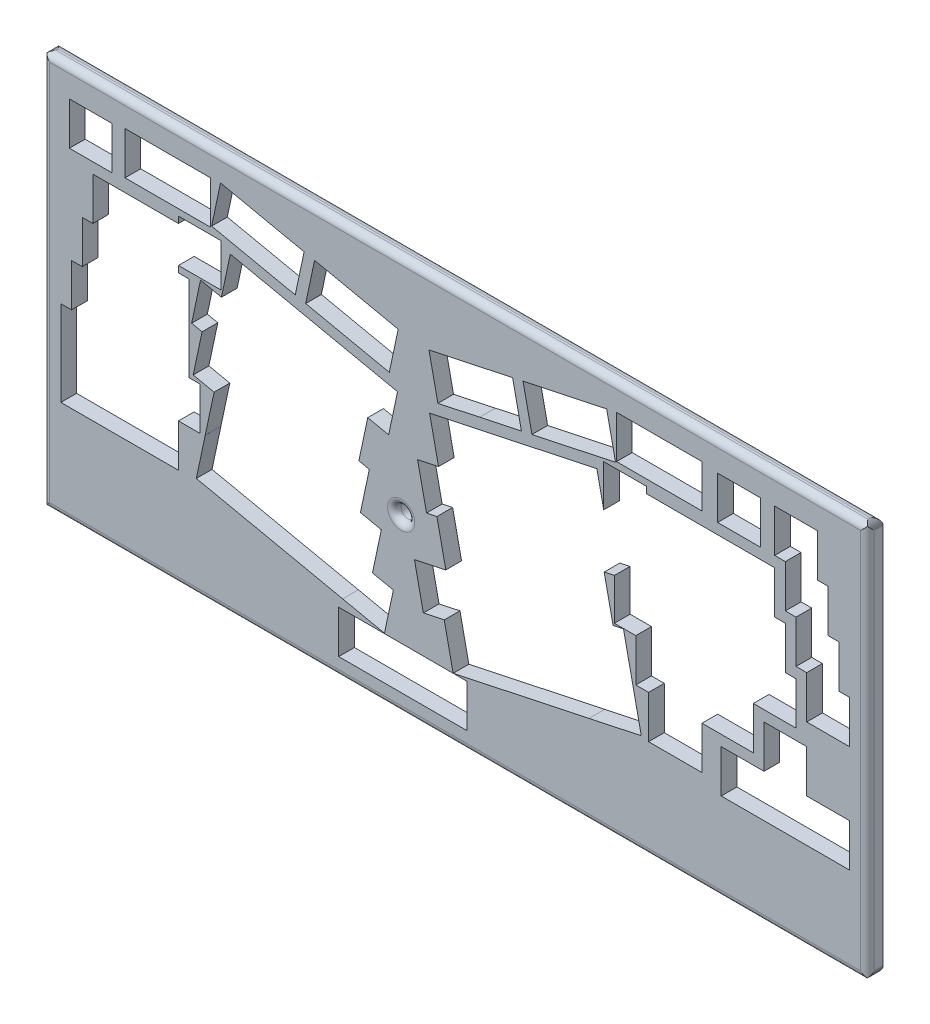
SolidWorks part; units mm, degrees
ref_plane "Front Plane" through (0, 0, 0) normal (0, 0, 1) x (1, 0, 0)
ref_plane "Top Plane" through (0, 0, 0) normal (0, 1, 0) x (1, 0, 0)
ref_plane "Right Plane" through (0, 0, 0) normal (1, 0, 0) x (0, 0, -1)
sketch "Model" plane through (0, 0, 0) normal (0, 0, 1) x (1, 0, 0)
  line L0 (364.568, 176.294) -> (364.804, 176.284)
  line L1 (364.804, 176.284) -> (365.037, 176.258)
  line L2 (365.037, 176.258) -> (365.27, 176.211)
  line L3 (365.27, 176.211) -> (365.495, 176.148)
  line L4 (365.495, 176.148) -> (365.718, 176.065)
  line L5 (365.718, 176.065) -> (365.933, 175.967)
  line L6 (365.933, 175.967) -> (366.134, 175.852)
  line L7 (366.134, 175.852) -> (366.332, 175.722)
  line L8 (366.332, 175.722) -> (366.518, 175.576)
  line L9 (366.518, 175.576) -> (366.688, 175.416)
  line L10 (366.688, 175.416) -> (366.85, 175.242)
  line L11 (366.85, 175.242) -> (366.995, 175.058)
  line L12 (366.995, 175.058) -> (367.125, 174.862)
  line L13 (367.125, 174.862) -> (367.242, 174.655)
  line L14 (367.242, 174.655) -> (367.34, 174.442)
  line L15 (367.34, 174.442) -> (367.422, 174.221)
  line L16 (367.422, 174.221) -> (367.485, 173.994)
  line L17 (367.485, 173.994) -> (367.531, 173.764)
  line L18 (367.531, 173.764) -> (367.559, 173.53)
  line L19 (367.559, 173.53) -> (367.57, 173.294)
  line L20 (367.57, 173.294) -> (367.57, 3.2728)
  line L21 (367.57, 3.2728) -> (367.559, 3.0372)
  line L22 (367.559, 3.0372) -> (367.531, 2.8029)
  line L23 (367.531, 2.8029) -> (367.485, 2.5728)
  line L24 (367.485, 2.5728) -> (367.422, 2.3454)
  line L25 (367.422, 2.3454) -> (367.34, 2.1249)
  line L26 (367.34, 2.1249) -> (367.242, 1.9113)
  line L27 (367.242, 1.9113) -> (367.125, 1.706)
  line L28 (367.125, 1.706) -> (366.995, 1.509)
  line L29 (366.995, 1.509) -> (366.85, 1.3243)
  line L30 (366.85, 1.3243) -> (366.688, 1.152)
  line L31 (366.688, 1.152) -> (366.518, 0.9908)
  line L32 (366.518, 0.9908) -> (366.332, 0.8447)
  line L33 (366.332, 0.8447) -> (366.134, 0.7152)
  line L34 (366.134, 0.7152) -> (365.933, 0.5994)
  line L35 (365.933, 0.5994) -> (365.718, 0.5016)
  line L36 (365.718, 0.5016) -> (365.495, 0.4189)
  line L37 (365.495, 0.4189) -> (365.27, 0.3555)
  line L38 (365.27, 0.3555) -> (365.037, 0.3101)
  line L39 (365.037, 0.3101) -> (364.804, 0.2825)
  line L40 (364.804, 0.2825) -> (364.568, 0.2729)
  line L41 (364.568, 0.2729) -> (3.0951, 0.2729)
  line L42 (3.0951, 0.2729) -> (2.8594, 0.2825)
  line L43 (2.8594, 0.2825) -> (2.6252, 0.3101)
  line L44 (2.6252, 0.3101) -> (2.395, 0.3555)
  line L45 (2.395, 0.3555) -> (2.1677, 0.4189)
  line L46 (2.1677, 0.4189) -> (1.9472, 0.5016)
  line L47 (1.9472, 0.5016) -> (1.7336, 0.5994)
  line L48 (1.7336, 0.5994) -> (1.5269, 0.7152)
  line L49 (1.5269, 0.7152) -> (1.3312, 0.8447)
  line L50 (1.3312, 0.8447) -> (1.1465, 0.9908)
  line L51 (1.1465, 0.9908) -> (0.9729, 1.152)
  line L52 (0.9729, 1.152) -> (0.813, 1.3243)
  line L53 (0.813, 1.3243) -> (0.667, 1.509)
  line L54 (0.667, 1.509) -> (0.5374, 1.706)
  line L55 (0.5374, 1.706) -> (0.4217, 1.9113)
  line L56 (0.4217, 1.9113) -> (0.3238, 2.1249)
  line L57 (0.3238, 2.1249) -> (0.2412, 2.3454)
  line L58 (0.2412, 2.3454) -> (0.1778, 2.5728)
  line L59 (0.1778, 2.5728) -> (0.1309, 2.8029)
  line L60 (0.1309, 2.8029) -> (0.1047, 3.0372)
  line L61 (0.1047, 3.0372) -> (0.0951, 3.2728)
  line L62 (0.0951, 3.2728) -> (0.0951, 173.294)
  line L63 (0.0951, 173.294) -> (0.1047, 173.53)
  line L64 (0.1047, 173.53) -> (0.1309, 173.764)
  line L65 (0.1309, 173.764) -> (0.1778, 173.994)
  line L66 (0.1778, 173.994) -> (0.2412, 174.221)
  line L67 (0.2412, 174.221) -> (0.3238, 174.442)
  line L68 (0.3238, 174.442) -> (0.4217, 174.655)
  line L69 (0.4217, 174.655) -> (0.5374, 174.862)
  line L70 (0.5374, 174.862) -> (0.667, 175.058)
  line L71 (0.667, 175.058) -> (0.813, 175.242)
  line L72 (0.813, 175.242) -> (0.9729, 175.416)
  line L73 (0.9729, 175.416) -> (1.1465, 175.576)
  line L74 (1.1465, 175.576) -> (1.3312, 175.722)
  line L75 (1.3312, 175.722) -> (1.5269, 175.852)
  line L76 (1.5269, 175.852) -> (1.7336, 175.967)
  line L77 (1.7336, 175.967) -> (1.9472, 176.065)
  line L78 (1.9472, 176.065) -> (2.1677, 176.148)
  line L79 (2.1677, 176.148) -> (2.395, 176.211)
  line L80 (2.395, 176.211) -> (2.6252, 176.258)
  line L81 (2.6252, 176.258) -> (2.8594, 176.284)
  line L82 (2.8594, 176.284) -> (3.0951, 176.294)
  line L83 (3.0951, 176.294) -> (364.568, 176.294)
  line L84 (3.7703, 5.271) -> (3.4782, 5.1222)
  line L85 (3.4782, 5.1222) -> (3.2453, 4.8907)
  line L86 (3.2453, 4.8907) -> (3.0951, 4.5972)
  line L87 (3.0951, 4.5972) -> (3.0441, 4.2719)
  line L88 (3.0441, 4.2719) -> (3.0951, 3.9481)
  line L89 (3.0951, 3.9481) -> (3.2453, 3.6559)
  line L90 (3.2453, 3.6559) -> (3.4782, 3.423)
  line L91 (3.4782, 3.423) -> (3.7703, 3.2742)
  line L92 (3.7703, 3.2742) -> (4.0955, 3.2218)
  line L93 (4.0955, 3.2218) -> (4.4193, 3.2742)
  line L94 (4.4193, 3.2742) -> (4.7129, 3.423)
  line L95 (4.7129, 3.423) -> (4.9444, 3.6559)
  line L96 (4.9444, 3.6559) -> (5.0932, 3.9481)
  line L97 (5.0932, 3.9481) -> (5.1456, 4.2719)
  line L98 (5.1456, 4.2719) -> (5.0932, 4.5972)
  line L99 (5.0932, 4.5972) -> (4.9444, 4.8907)
  line L100 (4.9444, 4.8907) -> (4.7129, 5.1222)
  line L101 (4.7129, 5.1222) -> (4.4193, 5.271)
  line L102 (4.4193, 5.271) -> (4.0955, 5.322)
  line L103 (4.0955, 5.322) -> (3.7703, 5.271)
  line L104 (75.6652, 5.271) -> (75.3731, 5.1222)
  line L105 (75.3731, 5.1222) -> (75.1403, 4.8907)
  line L106 (75.1403, 4.8907) -> (74.9914, 4.5972)
  line L107 (74.9914, 4.5972) -> (74.9392, 4.2719)
  line L108 (74.9392, 4.2719) -> (74.9914, 3.9481)
  line L109 (74.9914, 3.9481) -> (75.1403, 3.6559)
  line L110 (75.1403, 3.6559) -> (75.3731, 3.423)
  line L111 (75.3731, 3.423) -> (75.6652, 3.2742)
  line L112 (75.6652, 3.2742) -> (75.989, 3.2218)
  line L113 (75.989, 3.2218) -> (76.3143, 3.2742)
  line L114 (76.3143, 3.2742) -> (76.6064, 3.423)
  line L115 (76.6064, 3.423) -> (76.8396, 3.6559)
  line L116 (76.8396, 3.6559) -> (76.9881, 3.9481)
  line L117 (76.9881, 3.9481) -> (77.0393, 4.2719)
  line L118 (77.0393, 4.2719) -> (76.9881, 4.5972)
  line L119 (76.9881, 4.5972) -> (76.8396, 4.8907)
  line L120 (76.8396, 4.8907) -> (76.6064, 5.1222)
  line L121 (76.6064, 5.1222) -> (76.3143, 5.271)
  line L122 (76.3143, 5.271) -> (75.989, 5.322)
  line L123 (75.989, 5.322) -> (75.6652, 5.271)
  line L124 (147.559, 5.271) -> (147.267, 5.1222)
  line L125 (147.267, 5.1222) -> (147.034, 4.8907)
  line L126 (147.034, 4.8907) -> (146.885, 4.5972)
  line L127 (146.885, 4.5972) -> (146.834, 4.2719)
  line L128 (146.834, 4.2719) -> (146.885, 3.9481)
  line L129 (146.885, 3.9481) -> (147.034, 3.6559)
  line L130 (147.034, 3.6559) -> (147.267, 3.423)
  line L131 (147.267, 3.423) -> (147.559, 3.2742)
  line L132 (147.559, 3.2742) -> (147.884, 3.2218)
  line L133 (147.884, 3.2218) -> (148.208, 3.2742)
  line L134 (148.208, 3.2742) -> (148.501, 3.423)
  line L135 (148.501, 3.423) -> (148.733, 3.6559)
  line L136 (148.733, 3.6559) -> (148.883, 3.9481)
  line L137 (148.883, 3.9481) -> (148.934, 4.2719)
  line L138 (148.934, 4.2719) -> (148.883, 4.5972)
  line L139 (148.883, 4.5972) -> (148.733, 4.8907)
  line L140 (148.733, 4.8907) -> (148.501, 5.1222)
  line L141 (148.501, 5.1222) -> (148.208, 5.271)
  line L142 (148.208, 5.271) -> (147.884, 5.322)
  line L143 (147.884, 5.322) -> (147.559, 5.271)
  line L144 (219.454, 5.271) -> (219.162, 5.1222)
  line L145 (219.162, 5.1222) -> (218.929, 4.8907)
  line L146 (218.929, 4.8907) -> (218.78, 4.5972)
  line L147 (218.78, 4.5972) -> (218.729, 4.2719)
  line L148 (218.729, 4.2719) -> (218.78, 3.9481)
  line L149 (218.78, 3.9481) -> (218.929, 3.6559)
  line L150 (218.929, 3.6559) -> (219.162, 3.423)
  line L151 (219.162, 3.423) -> (219.454, 3.2742)
  line L152 (219.454, 3.2742) -> (219.779, 3.2218)
  line L153 (219.779, 3.2218) -> (220.103, 3.2742)
  line L154 (220.103, 3.2742) -> (220.396, 3.423)
  line L155 (220.396, 3.423) -> (220.628, 3.6559)
  line L156 (220.628, 3.6559) -> (220.777, 3.9481)
  line L157 (220.777, 3.9481) -> (220.829, 4.2719)
  line L158 (220.829, 4.2719) -> (220.777, 4.5972)
  line L159 (220.777, 4.5972) -> (220.628, 4.8907)
  line L160 (220.628, 4.8907) -> (220.396, 5.1222)
  line L161 (220.396, 5.1222) -> (220.103, 5.271)
  line L162 (220.103, 5.271) -> (219.779, 5.322)
  line L163 (219.779, 5.322) -> (219.454, 5.271)
  line L164 (291.349, 5.271) -> (291.057, 5.1222)
  line L165 (291.057, 5.1222) -> (290.824, 4.8907)
  line L166 (290.824, 4.8907) -> (290.675, 4.5972)
  line L167 (290.675, 4.5972) -> (290.624, 4.2719)
  line L168 (290.624, 4.2719) -> (290.675, 3.9481)
  line L169 (290.675, 3.9481) -> (290.824, 3.6559)
  line L170 (290.824, 3.6559) -> (291.057, 3.423)
  line L171 (291.057, 3.423) -> (291.349, 3.2742)
  line L172 (291.349, 3.2742) -> (291.673, 3.2218)
  line L173 (291.673, 3.2218) -> (291.998, 3.2742)
  line L174 (291.998, 3.2742) -> (292.29, 3.423)
  line L175 (292.29, 3.423) -> (292.523, 3.6559)
  line L176 (292.523, 3.6559) -> (292.672, 3.9481)
  line L177 (292.672, 3.9481) -> (292.723, 4.2719)
  line L178 (292.723, 4.2719) -> (292.672, 4.5972)
  line L179 (292.672, 4.5972) -> (292.523, 4.8907)
  line L180 (292.523, 4.8907) -> (292.29, 5.1222)
  line L181 (292.29, 5.1222) -> (291.998, 5.271)
  line L182 (291.998, 5.271) -> (291.673, 5.322)
  line L183 (291.673, 5.322) -> (291.349, 5.271)
  line L184 (363.245, 5.271) -> (362.952, 5.1222)
  line L185 (362.952, 5.1222) -> (362.719, 4.8907)
  line L186 (362.719, 4.8907) -> (362.571, 4.5972)
  line L187 (362.571, 4.5972) -> (362.518, 4.2719)
  line L188 (362.518, 4.2719) -> (362.571, 3.9481)
  line L189 (362.571, 3.9481) -> (362.719, 3.6559)
  line L190 (362.719, 3.6559) -> (362.952, 3.423)
  line L191 (362.952, 3.423) -> (363.245, 3.2742)
  line L192 (363.245, 3.2742) -> (363.569, 3.2218)
  line L193 (363.569, 3.2218) -> (363.894, 3.2742)
  line L194 (363.894, 3.2742) -> (364.187, 3.423)
  line L195 (364.187, 3.423) -> (364.419, 3.6559)
  line L196 (364.419, 3.6559) -> (364.568, 3.9481)
  line L197 (364.568, 3.9481) -> (364.617, 4.2719)
  line L198 (364.617, 4.2719) -> (364.568, 4.5972)
  line L199 (364.568, 4.5972) -> (364.419, 4.8907)
  line L200 (364.419, 4.8907) -> (364.187, 5.1222)
  line L201 (364.187, 5.1222) -> (363.894, 5.271)
  line L202 (363.894, 5.271) -> (363.569, 5.322)
  line L203 (363.569, 5.322) -> (363.245, 5.271)
  line L204 (131.918, 27.3237) -> (189.071, 27.3237)
  line L205 (189.071, 27.3237) -> (189.071, 8.2724)
  line L206 (189.071, 8.2724) -> (131.918, 8.2724)
  line L207 (131.918, 8.2724) -> (131.918, 27.3237)
  line L208 (250.03, 142.577) -> (250.03, 123.962)
  line L209 (250.03, 123.962) -> (246.978, 138.321)
  line L210 (246.978, 138.321) -> (228.344, 134.359)
  line L211 (228.344, 134.359) -> (228.344, 134.36)
  line L212 (228.344, 134.36) -> (209.71, 130.398)
  line L213 (209.71, 130.398) -> (209.71, 130.4)
  line L214 (209.71, 130.4) -> (172.441, 122.477)
  line L215 (172.441, 122.477) -> (176.401, 103.843)
  line L216 (176.401, 103.843) -> (167.084, 101.863)
  line L217 (167.084, 101.863) -> (171.045, 83.228)
  line L218 (171.045, 83.228) -> (175.704, 84.2176)
  line L219 (175.704, 84.2176) -> (179.664, 65.5849)
  line L220 (179.664, 65.5849) -> (165.688, 62.6152)
  line L221 (165.688, 62.6152) -> (169.649, 43.9787)
  line L222 (169.649, 43.9787) -> (178.966, 45.9602)
  line L223 (178.966, 45.9602) -> (182.928, 27.3265)
  line L224 (182.928, 27.3265) -> (243.487, 40.1987)
  line L225 (243.487, 40.1987) -> (266.781, 45.1499)
  line L226 (266.781, 45.1499) -> (258.859, 82.4191)
  line L227 (258.859, 82.4191) -> (254.201, 81.4296)
  line L228 (254.201, 81.4296) -> (250.242, 100.061)
  line L229 (250.242, 100.061) -> (254.791, 101.028)
  line L230 (254.791, 101.028) -> (254.791, 82.568)
  line L231 (254.791, 82.568) -> (264.316, 82.568)
  line L232 (264.316, 82.568) -> (264.316, 63.518)
  line L233 (264.316, 63.518) -> (270.032, 63.518)
  line L234 (270.032, 63.518) -> (270.032, 44.468)
  line L235 (270.032, 44.468) -> (293.846, 44.468)
  line L236 (293.846, 44.468) -> (293.846, 63.518)
  line L237 (293.846, 63.518) -> (316.706, 63.518)
  line L238 (316.706, 63.518) -> (316.706, 82.568)
  line L239 (316.706, 82.568) -> (335.756, 82.568)
  line L240 (335.756, 82.568) -> (335.756, 101.619)
  line L241 (335.756, 101.619) -> (330.994, 101.619)
  line L242 (330.994, 101.619) -> (330.994, 120.669)
  line L243 (330.994, 120.669) -> (326.231, 120.669)
  line L244 (326.231, 120.669) -> (326.231, 139.719)
  line L245 (326.231, 139.719) -> (269.081, 139.719)
  line L246 (269.081, 139.719) -> (269.081, 142.577)
  line L247 (269.081, 142.577) -> (250.03, 142.577)
  line L248 (79.6452, 120.829) -> (70.328, 122.811)
  line L249 (70.328, 122.811) -> (66.3677, 104.174)
  line L250 (66.3677, 104.174) -> (71.0269, 103.185)
  line L251 (71.0269, 103.185) -> (67.0648, 84.551)
  line L252 (67.0648, 84.551) -> (76.382, 82.5708)
  line L253 (76.382, 82.5708) -> (72.4214, 63.9367)
  line L254 (72.4214, 63.9367) -> (72.4228, 63.9367)
  line L255 (72.4228, 63.9367) -> (68.4611, 45.303)
  line L256 (68.4611, 45.303) -> (133.681, 31.4399)
  line L257 (133.681, 31.4399) -> (152.315, 27.4794)
  line L258 (152.315, 27.4794) -> (156.275, 46.1148)
  line L259 (156.275, 46.1148) -> (146.958, 48.0949)
  line L260 (146.958, 48.0949) -> (150.92, 66.7286)
  line L261 (150.92, 66.7286) -> (141.603, 68.7091)
  line L262 (141.603, 68.7091) -> (145.564, 87.3428)
  line L263 (145.564, 87.3428) -> (140.904, 88.3324)
  line L264 (140.904, 88.3324) -> (144.865, 106.965)
  line L265 (144.865, 106.965) -> (154.182, 104.985)
  line L266 (154.182, 104.985) -> (158.144, 123.621)
  line L267 (158.144, 123.621) -> (139.507, 127.581)
  line L268 (139.507, 127.581) -> (139.507, 127.58)
  line L269 (139.507, 127.58) -> (83.6069, 139.463)
  line L270 (83.6069, 139.463) -> (79.6452, 120.829)
  line L271 (321.466, 77.8069) -> (321.466, 58.7569)
  line L272 (321.466, 58.7569) -> (302.416, 58.7569)
  line L273 (302.416, 58.7569) -> (302.416, 39.7055)
  line L274 (302.416, 39.7055) -> (359.569, 39.7055)
  line L275 (359.569, 39.7055) -> (359.569, 58.7569)
  line L276 (359.569, 58.7569) -> (340.519, 58.7569)
  line L277 (340.519, 58.7569) -> (340.519, 77.8069)
  line L278 (340.519, 77.8069) -> (321.466, 77.8069)
  line L279 (60.4806, 142.577) -> (60.4806, 139.719)
  line L280 (60.4806, 139.719) -> (22.3821, 139.719)
  line L281 (22.3821, 139.719) -> (22.3821, 120.669)
  line L282 (22.3821, 120.669) -> (17.6196, 120.669)
  line L283 (17.6196, 120.669) -> (17.6196, 101.619)
  line L284 (17.6196, 101.619) -> (12.8571, 101.619)
  line L285 (12.8571, 101.619) -> (12.8571, 82.5694)
  line L286 (12.8571, 82.5694) -> (8.0946, 82.5694)
  line L287 (8.0946, 82.5694) -> (8.0946, 44.468)
  line L288 (8.0946, 44.468) -> (60.4834, 44.468)
  line L289 (60.4834, 44.468) -> (60.4834, 63.518)
  line L290 (60.4834, 63.518) -> (70.0084, 63.518)
  line L291 (70.0084, 63.518) -> (70.0084, 82.5694)
  line L292 (70.0084, 82.5694) -> (65.2459, 82.5694)
  line L293 (65.2459, 82.5694) -> (65.2459, 120.669)
  line L294 (65.2459, 120.669) -> (60.4834, 120.669)
  line L295 (60.4834, 120.669) -> (60.4834, 123.526)
  line L296 (60.4834, 123.526) -> (79.5334, 123.526)
  line L297 (79.5334, 123.526) -> (79.5334, 142.577)
  line L298 (79.5334, 142.577) -> (60.4806, 142.577)
  line L299 (3.7703, 89.2817) -> (3.4782, 89.1328)
  line L300 (3.4782, 89.1328) -> (3.2453, 88.9)
  line L301 (3.2453, 88.9) -> (3.0951, 88.6079)
  line L302 (3.0951, 88.6079) -> (3.0441, 88.284)
  line L303 (3.0441, 88.284) -> (3.0951, 87.9588)
  line L304 (3.0951, 87.9588) -> (3.2453, 87.6667)
  line L305 (3.2453, 87.6667) -> (3.4782, 87.4339)
  line L306 (3.4782, 87.4339) -> (3.7703, 87.285)
  line L307 (3.7703, 87.285) -> (4.0955, 87.2338)
  line L308 (4.0955, 87.2338) -> (4.4193, 87.285)
  line L309 (4.4193, 87.285) -> (4.7129, 87.4339)
  line L310 (4.7129, 87.4339) -> (4.9444, 87.6667)
  line L311 (4.9444, 87.6667) -> (5.0932, 87.9588)
  line L312 (5.0932, 87.9588) -> (5.1456, 88.284)
  line L313 (5.1456, 88.284) -> (5.0932, 88.6079)
  line L314 (5.0932, 88.6079) -> (4.9444, 88.9)
  line L315 (4.9444, 88.9) -> (4.7129, 89.1328)
  line L316 (4.7129, 89.1328) -> (4.4193, 89.2817)
  line L317 (4.4193, 89.2817) -> (4.0955, 89.3339)
  line L318 (4.0955, 89.3339) -> (3.7703, 89.2817)
  line L319 (363.245, 89.2817) -> (362.952, 89.1328)
  line L320 (362.952, 89.1328) -> (362.719, 88.9)
  line L321 (362.719, 88.9) -> (362.571, 88.6079)
  line L322 (362.571, 88.6079) -> (362.518, 88.284)
  line L323 (362.518, 88.284) -> (362.571, 87.9588)
  line L324 (362.571, 87.9588) -> (362.719, 87.6667)
  line L325 (362.719, 87.6667) -> (362.952, 87.4339)
  line L326 (362.952, 87.4339) -> (363.245, 87.285)
  line L327 (363.245, 87.285) -> (363.569, 87.2338)
  line L328 (363.569, 87.2338) -> (363.894, 87.285)
  line L329 (363.894, 87.285) -> (364.187, 87.4339)
  line L330 (364.187, 87.4339) -> (364.419, 87.6667)
  line L331 (364.419, 87.6667) -> (364.568, 87.9588)
  line L332 (364.568, 87.9588) -> (364.617, 88.284)
  line L333 (364.617, 88.284) -> (364.568, 88.6079)
  line L334 (364.568, 88.6079) -> (364.419, 88.9)
  line L335 (364.419, 88.9) -> (364.187, 89.1328)
  line L336 (364.187, 89.1328) -> (363.894, 89.2817)
  line L337 (363.894, 89.2817) -> (363.569, 89.3339)
  line L338 (363.569, 89.3339) -> (363.245, 89.2817)
  line L339 (326.228, 163.532) -> (326.228, 144.48)
  line L340 (326.228, 144.48) -> (330.991, 144.48)
  line L341 (330.991, 144.48) -> (330.991, 125.43)
  line L342 (330.991, 125.43) -> (335.755, 125.43)
  line L343 (335.755, 125.43) -> (335.755, 106.38)
  line L344 (335.755, 106.38) -> (340.516, 106.38)
  line L345 (340.516, 106.38) -> (340.516, 87.3305)
  line L346 (340.516, 87.3305) -> (359.569, 87.3305)
  line L347 (359.569, 87.3305) -> (359.569, 106.382)
  line L348 (359.569, 106.382) -> (354.806, 106.382)
  line L349 (354.806, 106.382) -> (354.806, 125.432)
  line L350 (354.806, 125.432) -> (350.044, 125.432)
  line L351 (350.044, 125.432) -> (350.044, 144.482)
  line L352 (350.044, 144.482) -> (345.281, 144.482)
  line L353 (345.281, 144.482) -> (345.281, 163.532)
  line L354 (345.281, 163.532) -> (326.228, 163.532)
  line L355 (269.08, 120.669) -> (264.316, 120.669)
  line L356 (264.316, 120.669) -> (264.316, 101.619)
  line L357 (264.316, 101.619) -> (257.572, 101.619)
  line L358 (257.572, 101.619) -> (264.215, 103.032)
  line L359 (264.215, 103.032) -> (260.255, 121.667)
  line L360 (260.255, 121.667) -> (250.938, 119.687)
  line L361 (250.938, 119.687) -> (250.122, 123.526)
  line L362 (250.122, 123.526) -> (269.08, 123.526)
  line L363 (269.08, 123.526) -> (269.08, 120.669)
  line L364 (172.147, 146.76) -> (176.109, 128.125)
  line L365 (176.109, 128.125) -> (194.743, 132.085)
  line L366 (194.743, 132.085) -> (213.378, 136.046)
  line L367 (213.378, 136.046) -> (209.418, 154.682)
  line L368 (209.418, 154.682) -> (172.147, 146.76)
  line L369 (117.205, 137.188) -> (154.474, 129.267)
  line L370 (154.474, 129.267) -> (158.436, 147.902)
  line L371 (158.436, 147.902) -> (121.167, 155.824)
  line L372 (121.167, 155.824) -> (117.205, 137.188)
  line L373 (214.074, 155.671) -> (218.035, 137.035)
  line L374 (218.035, 137.035) -> (255.305, 144.957)
  line L375 (255.305, 144.957) -> (251.343, 163.594)
  line L376 (251.343, 163.594) -> (214.074, 155.671)
  line L377 (75.2796, 146.101) -> (112.548, 138.179)
  line L378 (112.548, 138.179) -> (116.509, 156.814)
  line L379 (116.509, 156.814) -> (97.875, 160.776)
  line L380 (97.875, 160.776) -> (97.875, 160.774)
  line L381 (97.875, 160.774) -> (79.2399, 164.735)
  line L382 (79.2399, 164.735) -> (75.2796, 146.101)
  line L383 (300.798, 163.532) -> (319.849, 163.532)
  line L384 (319.849, 163.532) -> (319.849, 144.48)
  line L385 (319.849, 144.48) -> (300.798, 144.48)
  line L386 (300.798, 144.48) -> (300.798, 163.532)
  line L387 (11.9049, 163.532) -> (30.9563, 163.532)
  line L388 (30.9563, 163.532) -> (30.9563, 144.48)
  line L389 (30.9563, 144.48) -> (11.9049, 144.48)
  line L390 (11.9049, 144.48) -> (11.9049, 163.532)
  line L391 (255.744, 164.484) -> (293.846, 164.484)
  line L392 (293.846, 164.484) -> (293.846, 145.433)
  line L393 (293.846, 145.433) -> (255.744, 145.433)
  line L394 (255.744, 145.433) -> (255.744, 164.484)
  line L395 (36.6695, 164.484) -> (74.7709, 164.484)
  line L396 (74.7709, 164.484) -> (74.7709, 145.433)
  line L397 (74.7709, 145.433) -> (36.6695, 145.433)
  line L398 (36.6695, 145.433) -> (36.6695, 164.484)
  line L399 (3.7703, 173.294) -> (3.4782, 173.144)
  line L400 (3.4782, 173.144) -> (3.2453, 172.911)
  line L401 (3.2453, 172.911) -> (3.0951, 172.619)
  line L402 (3.0951, 172.619) -> (3.0441, 172.293)
  line L403 (3.0441, 172.293) -> (3.0951, 171.97)
  line L404 (3.0951, 171.97) -> (3.2453, 171.676)
  line L405 (3.2453, 171.676) -> (3.4782, 171.444)
  line L406 (3.4782, 171.444) -> (3.7703, 171.296)
  line L407 (3.7703, 171.296) -> (4.0955, 171.243)
  line L408 (4.0955, 171.243) -> (4.4193, 171.296)
  line L409 (4.4193, 171.296) -> (4.7129, 171.444)
  line L410 (4.7129, 171.444) -> (4.9444, 171.676)
  line L411 (4.9444, 171.676) -> (5.0932, 171.97)
  line L412 (5.0932, 171.97) -> (5.1456, 172.293)
  line L413 (5.1456, 172.293) -> (5.0932, 172.619)
  line L414 (5.0932, 172.619) -> (4.9444, 172.911)
  line L415 (4.9444, 172.911) -> (4.7129, 173.144)
  line L416 (4.7129, 173.144) -> (4.4193, 173.294)
  line L417 (4.4193, 173.294) -> (4.0955, 173.343)
  line L418 (4.0955, 173.343) -> (3.7703, 173.294)
  line L419 (363.245, 173.294) -> (362.952, 173.144)
  line L420 (362.952, 173.144) -> (362.719, 172.911)
  line L421 (362.719, 172.911) -> (362.571, 172.619)
  line L422 (362.571, 172.619) -> (362.518, 172.293)
  line L423 (362.518, 172.293) -> (362.571, 171.97)
  line L424 (362.571, 171.97) -> (362.719, 171.676)
  line L425 (362.719, 171.676) -> (362.952, 171.444)
  line L426 (362.952, 171.444) -> (363.245, 171.296)
  line L427 (363.245, 171.296) -> (363.569, 171.243)
  line L428 (363.569, 171.243) -> (363.894, 171.296)
  line L429 (363.894, 171.296) -> (364.187, 171.444)
  line L430 (364.187, 171.444) -> (364.419, 171.676)
  line L431 (364.419, 171.676) -> (364.568, 171.97)
  line L432 (364.568, 171.97) -> (364.617, 172.293)
  line L433 (364.617, 172.293) -> (364.568, 172.619)
  line L434 (364.568, 172.619) -> (364.419, 172.911)
  line L435 (364.419, 172.911) -> (364.187, 173.144)
  line L436 (364.187, 173.144) -> (363.894, 173.294)
  line L437 (363.894, 173.294) -> (363.569, 173.343)
  line L438 (363.569, 173.343) -> (363.245, 173.294)
  line L439 (291.349, 173.294) -> (291.057, 173.144)
  line L440 (291.057, 173.144) -> (290.824, 172.911)
  line L441 (290.824, 172.911) -> (290.675, 172.619)
  line L442 (290.675, 172.619) -> (290.624, 172.293)
  line L443 (290.624, 172.293) -> (290.675, 171.97)
  line L444 (290.675, 171.97) -> (290.824, 171.676)
  line L445 (290.824, 171.676) -> (291.057, 171.444)
  line L446 (291.057, 171.444) -> (291.349, 171.296)
  line L447 (291.349, 171.296) -> (291.673, 171.243)
  line L448 (291.673, 171.243) -> (291.998, 171.296)
  line L449 (291.998, 171.296) -> (292.29, 171.444)
  line L450 (292.29, 171.444) -> (292.523, 171.676)
  line L451 (292.523, 171.676) -> (292.672, 171.97)
  line L452 (292.672, 171.97) -> (292.723, 172.293)
  line L453 (292.723, 172.293) -> (292.672, 172.619)
  line L454 (292.672, 172.619) -> (292.523, 172.911)
  line L455 (292.523, 172.911) -> (292.29, 173.144)
  line L456 (292.29, 173.144) -> (291.998, 173.294)
  line L457 (291.998, 173.294) -> (291.673, 173.343)
  line L458 (291.673, 173.343) -> (291.349, 173.294)
  line L459 (219.454, 173.294) -> (219.162, 173.144)
  line L460 (219.162, 173.144) -> (218.929, 172.911)
  line L461 (218.929, 172.911) -> (218.78, 172.619)
  line L462 (218.78, 172.619) -> (218.729, 172.293)
  line L463 (218.729, 172.293) -> (218.78, 171.97)
  line L464 (218.78, 171.97) -> (218.929, 171.676)
  line L465 (218.929, 171.676) -> (219.162, 171.444)
  line L466 (219.162, 171.444) -> (219.454, 171.296)
  line L467 (219.454, 171.296) -> (219.779, 171.243)
  line L468 (219.779, 171.243) -> (220.103, 171.296)
  line L469 (220.103, 171.296) -> (220.396, 171.444)
  line L470 (220.396, 171.444) -> (220.628, 171.676)
  line L471 (220.628, 171.676) -> (220.777, 171.97)
  line L472 (220.777, 171.97) -> (220.829, 172.293)
  line L473 (220.829, 172.293) -> (220.777, 172.619)
  line L474 (220.777, 172.619) -> (220.628, 172.911)
  line L475 (220.628, 172.911) -> (220.396, 173.144)
  line L476 (220.396, 173.144) -> (220.103, 173.294)
  line L477 (220.103, 173.294) -> (219.779, 173.343)
  line L478 (219.779, 173.343) -> (219.454, 173.294)
  line L479 (147.559, 173.294) -> (147.267, 173.144)
  line L480 (147.267, 173.144) -> (147.034, 172.911)
  line L481 (147.034, 172.911) -> (146.885, 172.619)
  line L482 (146.885, 172.619) -> (146.834, 172.293)
  line L483 (146.834, 172.293) -> (146.885, 171.97)
  line L484 (146.885, 171.97) -> (147.034, 171.676)
  line L485 (147.034, 171.676) -> (147.267, 171.444)
  line L486 (147.267, 171.444) -> (147.559, 171.296)
  line L487 (147.559, 171.296) -> (147.884, 171.243)
  line L488 (147.884, 171.243) -> (148.208, 171.296)
  line L489 (148.208, 171.296) -> (148.501, 171.444)
  line L490 (148.501, 171.444) -> (148.733, 171.676)
  line L491 (148.733, 171.676) -> (148.883, 171.97)
  line L492 (148.883, 171.97) -> (148.934, 172.293)
  line L493 (148.934, 172.293) -> (148.883, 172.619)
  line L494 (148.883, 172.619) -> (148.733, 172.911)
  line L495 (148.733, 172.911) -> (148.501, 173.144)
  line L496 (148.501, 173.144) -> (148.208, 173.294)
  line L497 (148.208, 173.294) -> (147.884, 173.343)
  line L498 (147.884, 173.343) -> (147.559, 173.294)
  line L499 (75.6652, 173.294) -> (75.3731, 173.144)
  line L500 (75.3731, 173.144) -> (75.1403, 172.911)
  line L501 (75.1403, 172.911) -> (74.9914, 172.619)
  line L502 (74.9914, 172.619) -> (74.9392, 172.293)
  line L503 (74.9392, 172.293) -> (74.9914, 171.97)
  line L504 (74.9914, 171.97) -> (75.1403, 171.676)
  line L505 (75.1403, 171.676) -> (75.3731, 171.444)
  line L506 (75.3731, 171.444) -> (75.6652, 171.296)
  line L507 (75.6652, 171.296) -> (75.989, 171.243)
  line L508 (75.989, 171.243) -> (76.3143, 171.296)
  line L509 (76.3143, 171.296) -> (76.6064, 171.444)
  line L510 (76.6064, 171.444) -> (76.8396, 171.676)
  line L511 (76.8396, 171.676) -> (76.9881, 171.97)
  line L512 (76.9881, 171.97) -> (77.0393, 172.293)
  line L513 (77.0393, 172.293) -> (76.9881, 172.619)
  line L514 (76.9881, 172.619) -> (76.8396, 172.911)
  line L515 (76.8396, 172.911) -> (76.6064, 173.144)
  line L516 (76.6064, 173.144) -> (76.3143, 173.294)
  line L517 (76.3143, 173.294) -> (75.989, 173.343)
  line L518 (75.989, 173.343) -> (75.6652, 173.294)
  line L519 (364.568, 176.294) -> (364.804, 176.284)
  line L520 (364.804, 176.284) -> (365.037, 176.258)
  line L521 (365.037, 176.258) -> (365.27, 176.211)
  line L522 (365.27, 176.211) -> (365.495, 176.148)
  line L523 (365.495, 176.148) -> (365.718, 176.065)
  line L524 (365.718, 176.065) -> (365.933, 175.967)
  line L525 (365.933, 175.967) -> (366.134, 175.852)
  line L526 (366.134, 175.852) -> (366.332, 175.722)
  line L527 (366.332, 175.722) -> (366.518, 175.576)
  line L528 (366.518, 175.576) -> (366.688, 175.416)
  line L529 (366.688, 175.416) -> (366.85, 175.242)
  line L530 (366.85, 175.242) -> (366.995, 175.058)
  line L531 (366.995, 175.058) -> (367.125, 174.862)
  line L532 (367.125, 174.862) -> (367.242, 174.655)
  line L533 (367.242, 174.655) -> (367.34, 174.442)
  line L534 (367.34, 174.442) -> (367.422, 174.221)
  line L535 (367.422, 174.221) -> (367.485, 173.994)
  line L536 (367.485, 173.994) -> (367.531, 173.764)
  line L537 (367.531, 173.764) -> (367.559, 173.53)
  line L538 (367.559, 173.53) -> (367.57, 173.294)
  line L539 (367.57, 173.294) -> (367.57, 3.2728)
  line L540 (367.57, 3.2728) -> (367.559, 3.0372)
  line L541 (367.559, 3.0372) -> (367.531, 2.8029)
  line L542 (367.531, 2.8029) -> (367.485, 2.5728)
  line L543 (367.485, 2.5728) -> (367.422, 2.3454)
  line L544 (367.422, 2.3454) -> (367.34, 2.1249)
  line L545 (367.34, 2.1249) -> (367.242, 1.9113)
  line L546 (367.242, 1.9113) -> (367.125, 1.706)
  line L547 (367.125, 1.706) -> (366.995, 1.509)
  line L548 (366.995, 1.509) -> (366.85, 1.3243)
  line L549 (366.85, 1.3243) -> (366.688, 1.152)
  line L550 (366.688, 1.152) -> (366.518, 0.9908)
  line L551 (366.518, 0.9908) -> (366.332, 0.8447)
  line L552 (366.332, 0.8447) -> (366.134, 0.7152)
  line L553 (366.134, 0.7152) -> (365.933, 0.5994)
  line L554 (365.933, 0.5994) -> (365.718, 0.5016)
  line L555 (365.718, 0.5016) -> (365.495, 0.4189)
  line L556 (365.495, 0.4189) -> (365.27, 0.3555)
  line L557 (365.27, 0.3555) -> (365.037, 0.3101)
  line L558 (365.037, 0.3101) -> (364.804, 0.2825)
  line L559 (364.804, 0.2825) -> (364.568, 0.2729)
  line L560 (364.568, 0.2729) -> (3.0951, 0.2729)
  line L561 (3.0951, 0.2729) -> (2.8594, 0.2825)
  line L562 (2.8594, 0.2825) -> (2.6252, 0.3101)
  line L563 (2.6252, 0.3101) -> (2.395, 0.3555)
  line L564 (2.395, 0.3555) -> (2.1677, 0.4189)
  line L565 (2.1677, 0.4189) -> (1.9472, 0.5016)
  line L566 (1.9472, 0.5016) -> (1.7336, 0.5994)
  line L567 (1.7336, 0.5994) -> (1.5269, 0.7152)
  line L568 (1.5269, 0.7152) -> (1.3312, 0.8447)
  line L569 (1.3312, 0.8447) -> (1.1465, 0.9908)
  line L570 (1.1465, 0.9908) -> (0.9729, 1.152)
  line L571 (0.9729, 1.152) -> (0.813, 1.3243)
  line L572 (0.813, 1.3243) -> (0.667, 1.509)
  line L573 (0.667, 1.509) -> (0.5374, 1.706)
  line L574 (0.5374, 1.706) -> (0.4217, 1.9113)
  line L575 (0.4217, 1.9113) -> (0.3238, 2.1249)
  line L576 (0.3238, 2.1249) -> (0.2412, 2.3454)
  line L577 (0.2412, 2.3454) -> (0.1778, 2.5728)
  line L578 (0.1778, 2.5728) -> (0.1309, 2.8029)
  line L579 (0.1309, 2.8029) -> (0.1047, 3.0372)
  line L580 (0.1047, 3.0372) -> (0.0951, 3.2728)
  line L581 (0.0951, 3.2728) -> (0.0951, 173.294)
  line L582 (0.0951, 173.294) -> (0.1047, 173.53)
  line L583 (0.1047, 173.53) -> (0.1309, 173.764)
  line L584 (0.1309, 173.764) -> (0.1778, 173.994)
  line L585 (0.1778, 173.994) -> (0.2412, 174.221)
  line L586 (0.2412, 174.221) -> (0.3238, 174.442)
  line L587 (0.3238, 174.442) -> (0.4217, 174.655)
  line L588 (0.4217, 174.655) -> (0.5374, 174.862)
  line L589 (0.5374, 174.862) -> (0.667, 175.058)
  line L590 (0.667, 175.058) -> (0.813, 175.242)
  line L591 (0.813, 175.242) -> (0.9729, 175.416)
  line L592 (0.9729, 175.416) -> (1.1465, 175.576)
  line L593 (1.1465, 175.576) -> (1.3312, 175.722)
  line L594 (1.3312, 175.722) -> (1.5269, 175.852)
  line L595 (1.5269, 175.852) -> (1.7336, 175.967)
  line L596 (1.7336, 175.967) -> (1.9472, 176.065)
  line L597 (1.9472, 176.065) -> (2.1677, 176.148)
  line L598 (2.1677, 176.148) -> (2.395, 176.211)
  line L599 (2.395, 176.211) -> (2.6252, 176.258)
  line L600 (2.6252, 176.258) -> (2.8594, 176.284)
  line L601 (2.8594, 176.284) -> (3.0951, 176.294)
  line L602 (3.0951, 176.294) -> (364.568, 176.294)
  line L603 (3.7703, 5.271) -> (3.4782, 5.1222)
  line L604 (3.4782, 5.1222) -> (3.2453, 4.8907)
  line L605 (3.2453, 4.8907) -> (3.0951, 4.5972)
  line L606 (3.0951, 4.5972) -> (3.0441, 4.2719)
  line L607 (3.0441, 4.2719) -> (3.0951, 3.9481)
  line L608 (3.0951, 3.9481) -> (3.2453, 3.6559)
  line L609 (3.2453, 3.6559) -> (3.4782, 3.423)
  line L610 (3.4782, 3.423) -> (3.7703, 3.2742)
  line L611 (3.7703, 3.2742) -> (4.0955, 3.2218)
  line L612 (4.0955, 3.2218) -> (4.4193, 3.2742)
  line L613 (4.4193, 3.2742) -> (4.7129, 3.423)
  line L614 (4.7129, 3.423) -> (4.9444, 3.6559)
  line L615 (4.9444, 3.6559) -> (5.0932, 3.9481)
  line L616 (5.0932, 3.9481) -> (5.1456, 4.2719)
  line L617 (5.1456, 4.2719) -> (5.0932, 4.5972)
  line L618 (5.0932, 4.5972) -> (4.9444, 4.8907)
  line L619 (4.9444, 4.8907) -> (4.7129, 5.1222)
  line L620 (4.7129, 5.1222) -> (4.4193, 5.271)
  line L621 (4.4193, 5.271) -> (4.0955, 5.322)
  line L622 (4.0955, 5.322) -> (3.7703, 5.271)
  line L623 (75.6652, 5.271) -> (75.3731, 5.1222)
  line L624 (75.3731, 5.1222) -> (75.1403, 4.8907)
  line L625 (75.1403, 4.8907) -> (74.9914, 4.5972)
  line L626 (74.9914, 4.5972) -> (74.9392, 4.2719)
  line L627 (74.9392, 4.2719) -> (74.9914, 3.9481)
  line L628 (74.9914, 3.9481) -> (75.1403, 3.6559)
  line L629 (75.1403, 3.6559) -> (75.3731, 3.423)
  line L630 (75.3731, 3.423) -> (75.6652, 3.2742)
  line L631 (75.6652, 3.2742) -> (75.989, 3.2218)
  line L632 (75.989, 3.2218) -> (76.3143, 3.2742)
  line L633 (76.3143, 3.2742) -> (76.6064, 3.423)
  line L634 (76.6064, 3.423) -> (76.8396, 3.6559)
  line L635 (76.8396, 3.6559) -> (76.9881, 3.9481)
  line L636 (76.9881, 3.9481) -> (77.0393, 4.2719)
  line L637 (77.0393, 4.2719) -> (76.9881, 4.5972)
  line L638 (76.9881, 4.5972) -> (76.8396, 4.8907)
  line L639 (76.8396, 4.8907) -> (76.6064, 5.1222)
  line L640 (76.6064, 5.1222) -> (76.3143, 5.271)
  line L641 (76.3143, 5.271) -> (75.989, 5.322)
  line L642 (75.989, 5.322) -> (75.6652, 5.271)
  line L643 (147.559, 5.271) -> (147.267, 5.1222)
  line L644 (147.267, 5.1222) -> (147.034, 4.8907)
  line L645 (147.034, 4.8907) -> (146.885, 4.5972)
  line L646 (146.885, 4.5972) -> (146.834, 4.2719)
  line L647 (146.834, 4.2719) -> (146.885, 3.9481)
  line L648 (146.885, 3.9481) -> (147.034, 3.6559)
  line L649 (147.034, 3.6559) -> (147.267, 3.423)
  line L650 (147.267, 3.423) -> (147.559, 3.2742)
  line L651 (147.559, 3.2742) -> (147.884, 3.2218)
  line L652 (147.884, 3.2218) -> (148.208, 3.2742)
  line L653 (148.208, 3.2742) -> (148.501, 3.423)
  line L654 (148.501, 3.423) -> (148.733, 3.6559)
  line L655 (148.733, 3.6559) -> (148.883, 3.9481)
  line L656 (148.883, 3.9481) -> (148.934, 4.2719)
  line L657 (148.934, 4.2719) -> (148.883, 4.5972)
  line L658 (148.883, 4.5972) -> (148.733, 4.8907)
  line L659 (148.733, 4.8907) -> (148.501, 5.1222)
  line L660 (148.501, 5.1222) -> (148.208, 5.271)
  line L661 (148.208, 5.271) -> (147.884, 5.322)
  line L662 (147.884, 5.322) -> (147.559, 5.271)
  line L663 (219.454, 5.271) -> (219.162, 5.1222)
  line L664 (219.162, 5.1222) -> (218.929, 4.8907)
  line L665 (218.929, 4.8907) -> (218.78, 4.5972)
  line L666 (218.78, 4.5972) -> (218.729, 4.2719)
  line L667 (218.729, 4.2719) -> (218.78, 3.9481)
  line L668 (218.78, 3.9481) -> (218.929, 3.6559)
  line L669 (218.929, 3.6559) -> (219.162, 3.423)
  line L670 (219.162, 3.423) -> (219.454, 3.2742)
  line L671 (219.454, 3.2742) -> (219.779, 3.2218)
  line L672 (219.779, 3.2218) -> (220.103, 3.2742)
  line L673 (220.103, 3.2742) -> (220.396, 3.423)
  line L674 (220.396, 3.423) -> (220.628, 3.6559)
  line L675 (220.628, 3.6559) -> (220.777, 3.9481)
  line L676 (220.777, 3.9481) -> (220.829, 4.2719)
  line L677 (220.829, 4.2719) -> (220.777, 4.5972)
  line L678 (220.777, 4.5972) -> (220.628, 4.8907)
  line L679 (220.628, 4.8907) -> (220.396, 5.1222)
  line L680 (220.396, 5.1222) -> (220.103, 5.271)
  line L681 (220.103, 5.271) -> (219.779, 5.322)
  line L682 (219.779, 5.322) -> (219.454, 5.271)
  line L683 (291.349, 5.271) -> (291.057, 5.1222)
  line L684 (291.057, 5.1222) -> (290.824, 4.8907)
  line L685 (290.824, 4.8907) -> (290.675, 4.5972)
  line L686 (290.675, 4.5972) -> (290.624, 4.2719)
  line L687 (290.624, 4.2719) -> (290.675, 3.9481)
  line L688 (290.675, 3.9481) -> (290.824, 3.6559)
  line L689 (290.824, 3.6559) -> (291.057, 3.423)
  line L690 (291.057, 3.423) -> (291.349, 3.2742)
  line L691 (291.349, 3.2742) -> (291.673, 3.2218)
  line L692 (291.673, 3.2218) -> (291.998, 3.2742)
  line L693 (291.998, 3.2742) -> (292.29, 3.423)
  line L694 (292.29, 3.423) -> (292.523, 3.6559)
  line L695 (292.523, 3.6559) -> (292.672, 3.9481)
  line L696 (292.672, 3.9481) -> (292.723, 4.2719)
  line L697 (292.723, 4.2719) -> (292.672, 4.5972)
  line L698 (292.672, 4.5972) -> (292.523, 4.8907)
  line L699 (292.523, 4.8907) -> (292.29, 5.1222)
  line L700 (292.29, 5.1222) -> (291.998, 5.271)
  line L701 (291.998, 5.271) -> (291.673, 5.322)
  line L702 (291.673, 5.322) -> (291.349, 5.271)
  line L703 (363.245, 5.271) -> (362.952, 5.1222)
  line L704 (362.952, 5.1222) -> (362.719, 4.8907)
  line L705 (362.719, 4.8907) -> (362.571, 4.5972)
  line L706 (362.571, 4.5972) -> (362.518, 4.2719)
  line L707 (362.518, 4.2719) -> (362.571, 3.9481)
  line L708 (362.571, 3.9481) -> (362.719, 3.6559)
  line L709 (362.719, 3.6559) -> (362.952, 3.423)
  line L710 (362.952, 3.423) -> (363.245, 3.2742)
  line L711 (363.245, 3.2742) -> (363.569, 3.2218)
  line L712 (363.569, 3.2218) -> (363.894, 3.2742)
  line L713 (363.894, 3.2742) -> (364.187, 3.423)
  line L714 (364.187, 3.423) -> (364.419, 3.6559)
  line L715 (364.419, 3.6559) -> (364.568, 3.9481)
  line L716 (364.568, 3.9481) -> (364.617, 4.2719)
  line L717 (364.617, 4.2719) -> (364.568, 4.5972)
  line L718 (364.568, 4.5972) -> (364.419, 4.8907)
  line L719 (364.419, 4.8907) -> (364.187, 5.1222)
  line L720 (364.187, 5.1222) -> (363.894, 5.271)
  line L721 (363.894, 5.271) -> (363.569, 5.322)
  line L722 (363.569, 5.322) -> (363.245, 5.271)
  line L723 (3.7703, 89.2817) -> (3.4782, 89.1328)
  line L724 (3.4782, 89.1328) -> (3.2453, 88.9)
  line L725 (3.2453, 88.9) -> (3.0951, 88.6079)
  line L726 (3.0951, 88.6079) -> (3.0441, 88.284)
  line L727 (3.0441, 88.284) -> (3.0951, 87.9588)
  line L728 (3.0951, 87.9588) -> (3.2453, 87.6667)
  line L729 (3.2453, 87.6667) -> (3.4782, 87.4339)
  line L730 (3.4782, 87.4339) -> (3.7703, 87.285)
  line L731 (3.7703, 87.285) -> (4.0955, 87.2338)
  line L732 (4.0955, 87.2338) -> (4.4193, 87.285)
  line L733 (4.4193, 87.285) -> (4.7129, 87.4339)
  line L734 (4.7129, 87.4339) -> (4.9444, 87.6667)
  line L735 (4.9444, 87.6667) -> (5.0932, 87.9588)
  line L736 (5.0932, 87.9588) -> (5.1456, 88.284)
  line L737 (5.1456, 88.284) -> (5.0932, 88.6079)
  line L738 (5.0932, 88.6079) -> (4.9444, 88.9)
  line L739 (4.9444, 88.9) -> (4.7129, 89.1328)
  line L740 (4.7129, 89.1328) -> (4.4193, 89.2817)
  line L741 (4.4193, 89.2817) -> (4.0955, 89.3339)
  line L742 (4.0955, 89.3339) -> (3.7703, 89.2817)
  line L743 (363.245, 89.2817) -> (362.952, 89.1328)
  line L744 (362.952, 89.1328) -> (362.719, 88.9)
  line L745 (362.719, 88.9) -> (362.571, 88.6079)
  line L746 (362.571, 88.6079) -> (362.518, 88.284)
  line L747 (362.518, 88.284) -> (362.571, 87.9588)
  line L748 (362.571, 87.9588) -> (362.719, 87.6667)
  line L749 (362.719, 87.6667) -> (362.952, 87.4339)
  line L750 (362.952, 87.4339) -> (363.245, 87.285)
  line L751 (363.245, 87.285) -> (363.569, 87.2338)
  line L752 (363.569, 87.2338) -> (363.894, 87.285)
  line L753 (363.894, 87.285) -> (364.187, 87.4339)
  line L754 (364.187, 87.4339) -> (364.419, 87.6667)
  line L755 (364.419, 87.6667) -> (364.568, 87.9588)
  line L756 (364.568, 87.9588) -> (364.617, 88.284)
  line L757 (364.617, 88.284) -> (364.568, 88.6079)
  line L758 (364.568, 88.6079) -> (364.419, 88.9)
  line L759 (364.419, 88.9) -> (364.187, 89.1328)
  line L760 (364.187, 89.1328) -> (363.894, 89.2817)
  line L761 (363.894, 89.2817) -> (363.569, 89.3339)
  line L762 (363.569, 89.3339) -> (363.245, 89.2817)
  line L763 (3.7703, 173.294) -> (3.4782, 173.144)
  line L764 (3.4782, 173.144) -> (3.2453, 172.911)
  line L765 (3.2453, 172.911) -> (3.0951, 172.619)
  line L766 (3.0951, 172.619) -> (3.0441, 172.293)
  line L767 (3.0441, 172.293) -> (3.0951, 171.97)
  line L768 (3.0951, 171.97) -> (3.2453, 171.676)
  line L769 (3.2453, 171.676) -> (3.4782, 171.444)
  line L770 (3.4782, 171.444) -> (3.7703, 171.296)
  line L771 (3.7703, 171.296) -> (4.0955, 171.243)
  line L772 (4.0955, 171.243) -> (4.4193, 171.296)
  line L773 (4.4193, 171.296) -> (4.7129, 171.444)
  line L774 (4.7129, 171.444) -> (4.9444, 171.676)
  line L775 (4.9444, 171.676) -> (5.0932, 171.97)
  line L776 (5.0932, 171.97) -> (5.1456, 172.293)
  line L777 (5.1456, 172.293) -> (5.0932, 172.619)
  line L778 (5.0932, 172.619) -> (4.9444, 172.911)
  line L779 (4.9444, 172.911) -> (4.7129, 173.144)
  line L780 (4.7129, 173.144) -> (4.4193, 173.294)
  line L781 (4.4193, 173.294) -> (4.0955, 173.343)
  line L782 (4.0955, 173.343) -> (3.7703, 173.294)
  line L783 (363.245, 173.294) -> (362.952, 173.144)
  line L784 (362.952, 173.144) -> (362.719, 172.911)
  line L785 (362.719, 172.911) -> (362.571, 172.619)
  line L786 (362.571, 172.619) -> (362.518, 172.293)
  line L787 (362.518, 172.293) -> (362.571, 171.97)
  line L788 (362.571, 171.97) -> (362.719, 171.676)
  line L789 (362.719, 171.676) -> (362.952, 171.444)
  line L790 (362.952, 171.444) -> (363.245, 171.296)
  line L791 (363.245, 171.296) -> (363.569, 171.243)
  line L792 (363.569, 171.243) -> (363.894, 171.296)
  line L793 (363.894, 171.296) -> (364.187, 171.444)
  line L794 (364.187, 171.444) -> (364.419, 171.676)
  line L795 (364.419, 171.676) -> (364.568, 171.97)
  line L796 (364.568, 171.97) -> (364.617, 172.293)
  line L797 (364.617, 172.293) -> (364.568, 172.619)
  line L798 (364.568, 172.619) -> (364.419, 172.911)
  line L799 (364.419, 172.911) -> (364.187, 173.144)
  line L800 (364.187, 173.144) -> (363.894, 173.294)
  line L801 (363.894, 173.294) -> (363.569, 173.343)
  line L802 (363.569, 173.343) -> (363.245, 173.294)
  line L803 (291.349, 173.294) -> (291.057, 173.144)
  line L804 (291.057, 173.144) -> (290.824, 172.911)
  line L805 (290.824, 172.911) -> (290.675, 172.619)
  line L806 (290.675, 172.619) -> (290.624, 172.293)
  line L807 (290.624, 172.293) -> (290.675, 171.97)
  line L808 (290.675, 171.97) -> (290.824, 171.676)
  line L809 (290.824, 171.676) -> (291.057, 171.444)
  line L810 (291.057, 171.444) -> (291.349, 171.296)
  line L811 (291.349, 171.296) -> (291.673, 171.243)
  line L812 (291.673, 171.243) -> (291.998, 171.296)
  line L813 (291.998, 171.296) -> (292.29, 171.444)
  line L814 (292.29, 171.444) -> (292.523, 171.676)
  line L815 (292.523, 171.676) -> (292.672, 171.97)
  line L816 (292.672, 171.97) -> (292.723, 172.293)
  line L817 (292.723, 172.293) -> (292.672, 172.619)
  line L818 (292.672, 172.619) -> (292.523, 172.911)
  line L819 (292.523, 172.911) -> (292.29, 173.144)
  line L820 (292.29, 173.144) -> (291.998, 173.294)
  line L821 (291.998, 173.294) -> (291.673, 173.343)
  line L822 (291.673, 173.343) -> (291.349, 173.294)
  line L823 (219.454, 173.294) -> (219.162, 173.144)
  line L824 (219.162, 173.144) -> (218.929, 172.911)
  line L825 (218.929, 172.911) -> (218.78, 172.619)
  line L826 (218.78, 172.619) -> (218.729, 172.293)
  line L827 (218.729, 172.293) -> (218.78, 171.97)
  line L828 (218.78, 171.97) -> (218.929, 171.676)
  line L829 (218.929, 171.676) -> (219.162, 171.444)
  line L830 (219.162, 171.444) -> (219.454, 171.296)
  line L831 (219.454, 171.296) -> (219.779, 171.243)
  line L832 (219.779, 171.243) -> (220.103, 171.296)
  line L833 (220.103, 171.296) -> (220.396, 171.444)
  line L834 (220.396, 171.444) -> (220.628, 171.676)
  line L835 (220.628, 171.676) -> (220.777, 171.97)
  line L836 (220.777, 171.97) -> (220.829, 172.293)
  line L837 (220.829, 172.293) -> (220.777, 172.619)
  line L838 (220.777, 172.619) -> (220.628, 172.911)
  line L839 (220.628, 172.911) -> (220.396, 173.144)
  line L840 (220.396, 173.144) -> (220.103, 173.294)
  line L841 (220.103, 173.294) -> (219.779, 173.343)
  line L842 (219.779, 173.343) -> (219.454, 173.294)
  line L843 (147.559, 173.294) -> (147.267, 173.144)
  line L844 (147.267, 173.144) -> (147.034, 172.911)
  line L845 (147.034, 172.911) -> (146.885, 172.619)
  line L846 (146.885, 172.619) -> (146.834, 172.293)
  line L847 (146.834, 172.293) -> (146.885, 171.97)
  line L848 (146.885, 171.97) -> (147.034, 171.676)
  line L849 (147.034, 171.676) -> (147.267, 171.444)
  line L850 (147.267, 171.444) -> (147.559, 171.296)
  line L851 (147.559, 171.296) -> (147.884, 171.243)
  line L852 (147.884, 171.243) -> (148.208, 171.296)
  line L853 (148.208, 171.296) -> (148.501, 171.444)
  line L854 (148.501, 171.444) -> (148.733, 171.676)
  line L855 (148.733, 171.676) -> (148.883, 171.97)
  line L856 (148.883, 171.97) -> (148.934, 172.293)
  line L857 (148.934, 172.293) -> (148.883, 172.619)
  line L858 (148.883, 172.619) -> (148.733, 172.911)
  line L859 (148.733, 172.911) -> (148.501, 173.144)
  line L860 (148.501, 173.144) -> (148.208, 173.294)
  line L861 (148.208, 173.294) -> (147.884, 173.343)
  line L862 (147.884, 173.343) -> (147.559, 173.294)
  line L863 (75.6652, 173.294) -> (75.3731, 173.144)
  line L864 (75.3731, 173.144) -> (75.1403, 172.911)
  line L865 (75.1403, 172.911) -> (74.9914, 172.619)
  line L866 (74.9914, 172.619) -> (74.9392, 172.293)
  line L867 (74.9392, 172.293) -> (74.9914, 171.97)
  line L868 (74.9914, 171.97) -> (75.1403, 171.676)
  line L869 (75.1403, 171.676) -> (75.3731, 171.444)
  line L870 (75.3731, 171.444) -> (75.6652, 171.296)
  line L871 (75.6652, 171.296) -> (75.989, 171.243)
  line L872 (75.989, 171.243) -> (76.3143, 171.296)
  line L873 (76.3143, 171.296) -> (76.6064, 171.444)
  line L874 (76.6064, 171.444) -> (76.8396, 171.676)
  line L875 (76.8396, 171.676) -> (76.9881, 171.97)
  line L876 (76.9881, 171.97) -> (77.0393, 172.293)
  line L877 (77.0393, 172.293) -> (76.9881, 172.619)
  line L878 (76.9881, 172.619) -> (76.8396, 172.911)
  line L879 (76.8396, 172.911) -> (76.6064, 173.144)
  line L880 (76.6064, 173.144) -> (76.3143, 173.294)
  line L881 (76.3143, 173.294) -> (75.989, 173.343)
  line L882 (75.989, 173.343) -> (75.6652, 173.294)
  circle A0 centre (159.7611, 76.9187) radius 3.048
extrude "凸台-拉伸1" add sketch "Model" along normal blind 7 contours L83 L82 L81 L80 L79 L78 L77 L76 L75 L74 L73 L72 L71 L70 L69 L68 L67 L66 L65 L64 L63 L62 L61 L60 L59 L58 L57 L56 L55 L54 L53 L52 L51 L50 L49 L48 L47 L46 L45 L44 L43 L42 L41 L40 L39 L38 L37 L36 L35 L34 L33 | L102 L103 L84 L85 L86 L87 L88 L89 L90 L91 L92 L93 L94 L95 L96 L97 L98 L99 L100 L101 | L122 L123 L104 L105 L106 L107 L108 L109 L110 L111 L112 L113 L114 L115 L116 L117 L118 L119 L120 L121 | L142 L143 L124 L125 L126 L127 L128 L129 L130 L131 L132 L133 L134 L135 L136 L137 L138 L139 L140 L141 | L162 L163 L144 L145 L146 L147 L148 L149 L150 L151 L152 L153 L154 L155 L156 L157 L158 L159 L160 L161 | L182 L183 L164 L165 L166 L167 L168 L169 L170 L171 L172 L173 L174 L175 L176 L177 L178 L179 L180 L181 | L202 L203 L184 L185 L186 L187 L188 L189 L190 L191 L192 L193 L194 L195 L196 L197 L198 L199 L200 L201 | L337 L338 L319 L320 L321 L322 L323 L324 L325 L326 L327 L328 L329 L330 L331 L332 L333 L334 L335 L336 | L437 L438 L419 L420 L421 L422 L423 L424 L425 L426 L427 L428 L429 L430 L431 L432 L433 L434 L435 L436 | L457 L458 L439 L440 L441 L442 L443 L444 L445 L446 L447 L448 L449 L450 L451 L452 L453 L454 L455 L456 | L477 L478 L459 L460 L461 L462 L463 L464 L465 L466 L467 L468 L469 L470 L471 L472 L473 L474 L475 L476 | L497 L498 L479 L480 L481 L482 L483 L484 L485 L486 L487 L488 L489 L490 L491 L492 L493 L494 L495 L496 | L517 L518 L499 L500 L501 L502 L503 L504 L505 L506 L507 L508 L509 L510 L511 L512 L513 L514 L515 L516 | L417 L418 L399 L400 L401 L402 L403 L404 L405 L406 L407 L408 L409 L410 L411 L412 L413 L414 L415 L416 | L317 L318 L299 L300 L301 L302 L303 L304 L305 L306 L307 L308 L309 L310 L311 L312 L313 L314 L315 L316 region at (364.6688, 175.8819, 0) region at (4.0947, 4.2726, 0) region at (75.9897, 4.2726, 0) region at (147.8838, 4.2726, 0) region at (219.7787, 4.2726, 0) region at (291.6735, 4.2726, 0) region at (363.569, 4.2726, 0) region at (4.0947, 88.2835, 0) region at (363.569, 88.2835, 0) region at (4.0947, 172.2941, 0) region at (363.569, 172.2941, 0) region at (291.6735, 172.2941, 0) region at (219.7787, 172.2941, 0) region at (147.8838, 172.2941, 0) region at (75.9897, 172.2941, 0)
sketch "草图4" plane through (0, 0, 0) normal (0, 0, -1) x (-1, 0, 0)
  line L0 (-292.723, 4.2719) -> (-290.624, 4.2719) construction
  line L1 (-220.829, 4.2719) -> (-218.729, 4.2719) construction
  line L2 (-148.934, 4.2719) -> (-146.834, 4.2719) construction
  line L3 (-77.0393, 4.2719) -> (-74.9392, 4.2719) construction
  line L4 (-5.1456, 4.2719) -> (-3.0441, 4.2719) construction
  line L5 (-5.1456, 88.284) -> (-3.0441, 88.284) construction
  line L6 (-5.1456, 172.293) -> (-3.0441, 172.293) construction
  line L7 (-77.0393, 172.293) -> (-74.9392, 172.293) construction
  line L8 (-148.934, 172.293) -> (-146.834, 172.293) construction
  line L9 (-219.779, 173.343) -> (-219.779, 171.243) construction
  line L11 (-291.673, 173.343) -> (-291.673, 171.243) construction
  line L12 (-363.569, 173.343) -> (-363.569, 171.243) construction
  line L13 (-363.569, 89.3339) -> (-363.569, 87.2338) construction
  circle A0 centre (-363.5699, 4.2751) radius 1.45
  circle A1 centre (-291.673, 4.2719) radius 1.45
  circle A2 centre (-219.779, 4.2719) radius 1.45
  circle A3 centre (-147.884, 4.2719) radius 1.45
  circle A4 centre (-75.9892, 4.2719) radius 1.45
  circle A5 centre (-4.0948, 4.2719) radius 1.45
  circle A6 centre (-4.0948, 88.284) radius 1.45
  circle A7 centre (-4.0948, 172.293) radius 1.45
  circle A8 centre (-75.9892, 172.293) radius 1.45
  circle A9 centre (-147.884, 172.293) radius 1.45
  circle A10 centre (-219.779, 172.293) radius 1.45
  circle A11 centre (-291.673, 172.293) radius 1.45
  circle A12 centre (-363.569, 172.293) radius 1.45
  circle A13 centre (-363.569, 88.2839) radius 1.45
extrude "切除-拉伸1" cut sketch "草图4" against normal blind 4
fillet "圆角1" radius 3 14 edges at (183.8315, 176.294, 0) (0.0951, 88.2834, 0) (183.8315, 0.2729, 0) (3.0951, 0.2729, 3.5) (183.8315, 0.2729, 7) (364.568, 0.2729, 3.5) (0.0951, 173.294, 3.5) (0.0951, 88.2834, 7) (0.0951, 3.2728, 3.5) (364.568, 176.294, 3.5) (183.8315, 176.294, 7) (3.0951, 176.294, 3.5) (367.57, 88.2834, 7) (162.8091, 76.9187, 7)
